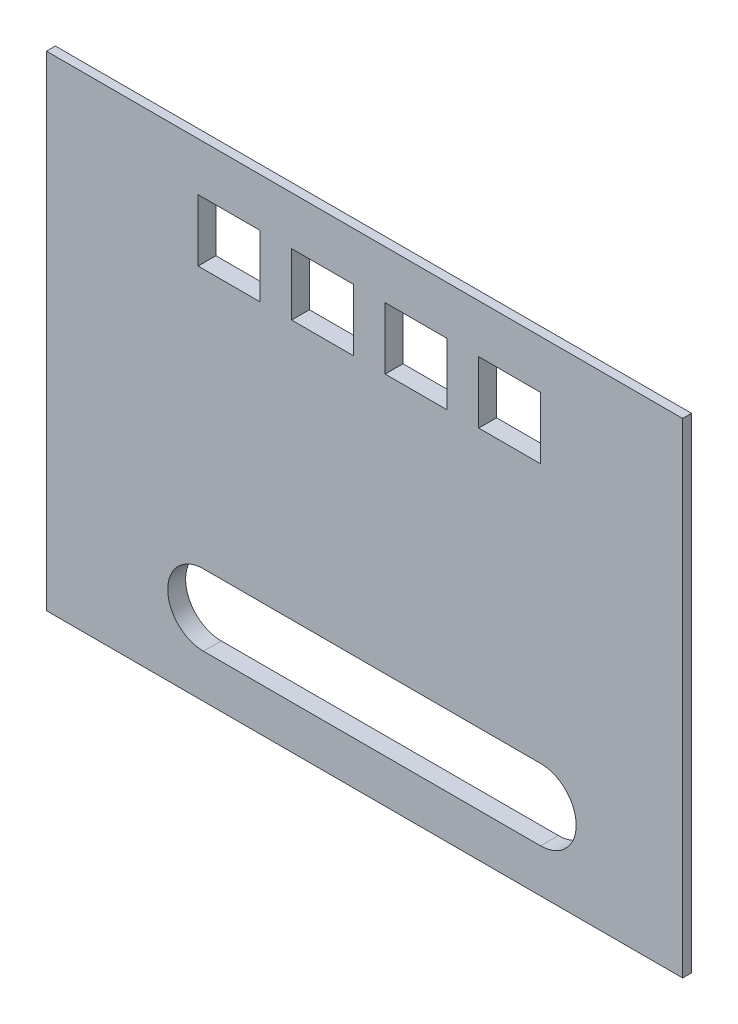
SolidWorks part; units mm, degrees
ref_plane "Спереди" through (0, 0, 0) normal (0, 0, 1) x (1, 0, 0)
ref_plane "Сверху" through (0, 0, 0) normal (0, 1, 0) x (1, 0, 0)
ref_plane "Справа" through (0, 0, 0) normal (1, 0, 0) x (0, 0, -1)
other "Configuration Table"
sketch "Эскиз1" plane through (0, 0, 0) normal (0, 0, 1) x (1, 0, 0)
  line L1 (3, 3) -> (104, 3)
  line L2 (3, 3) -> (3, 77)
  line L3 (3, 77) -> (104, 77)
  line L4 (104, 3) -> (104, 77)
extrude "Бобышка-Вытянуть1" add sketch "Эскиз1" along normal blind 3
sketch "Эскиз2" plane through (0, 0, 0) normal (0, 0, 1) x (1, 0, 0)
  line L1 (0, 0) -> (107, 0)
  line L2 (0, 0) -> (0, 80)
  line L3 (0, 80) -> (107, 80)
  line L4 (107, 0) -> (107, 80)
extrude "Бобышка-Вытянуть2" add sketch "Эскиз2" along normal blind 1.5 from offset 1.5
sketch "Эскиз3" plane through (0, 0, 3) normal (0, 0, 1) x (1, 0, 0)
  line L0 (26.4, 13.3) -> (83.1, 13.3) construction
  line L1 (25.5, 62.95) -> (35.9, 62.95)
  line L2 (25.5, 62.95) -> (25.5, 73.35)
  line L3 (25.5, 73.35) -> (35.9, 73.35)
  line L4 (35.9, 62.95) -> (35.9, 73.35)
  line L5 (41.233, 62.95) -> (51.633, 62.95)
  line L6 (41.233, 62.95) -> (41.233, 73.35)
  line L7 (41.233, 73.35) -> (51.633, 73.35)
  line L8 (51.633, 62.95) -> (51.633, 73.35)
  line L9 (56.967, 62.95) -> (67.367, 62.95)
  line L10 (56.967, 62.95) -> (56.967, 73.35)
  line L11 (56.967, 73.35) -> (67.367, 73.35)
  line L12 (67.367, 62.95) -> (67.367, 73.35)
  line L13 (72.7, 62.95) -> (83.1, 62.95)
  line L14 (72.7, 62.95) -> (72.7, 73.35)
  line L15 (72.7, 73.35) -> (83.1, 73.35)
  line L16 (83.1, 62.95) -> (83.1, 73.35)
  line L17 (26.4, 19.3) -> (83.1, 19.3)
  line L18 (26.4, 7.3) -> (83.1, 7.3)
  arc A0 (26.4, 19.3) -> (26.4, 7.3) centre (26.4, 13.3) ccw
  arc A1 (83.1, 7.3) -> (83.1, 19.3) centre (83.1, 13.3) ccw
  point P18 (54.75, 13.3)
extrude "Вырез-Вытянуть1" cut sketch "Эскиз3" against normal blind 5
sketch "Эскиз4" plane through (0, 0, 0) normal (0, 0, 1) x (1, 0, 0)
  line L1 (3, 77) -> (104, 77)
  line L2 (3, 77) -> (3, 78.5)
  line L3 (3, 78.5) -> (104, 78.5)
  line L4 (104, 77) -> (104, 78.5)
extrude "top_rear_inner_extension_1p5mm" add sketch "Эскиз4" along normal blind 3
sketch "Эскиз5" plane through (0, 0, 0) normal (0, 0, 1) x (1, 0, 0)
  line L1 (0, 80) -> (107, 80)
  line L2 (0, 80) -> (0, 81.5)
  line L3 (0, 81.5) -> (107, 81.5)
  line L4 (107, 80) -> (107, 81.5)
extrude "top_rear_outer_skin_extension_1p5mm" add sketch "Эскиз5" along normal blind 1.5 from offset 1.5
